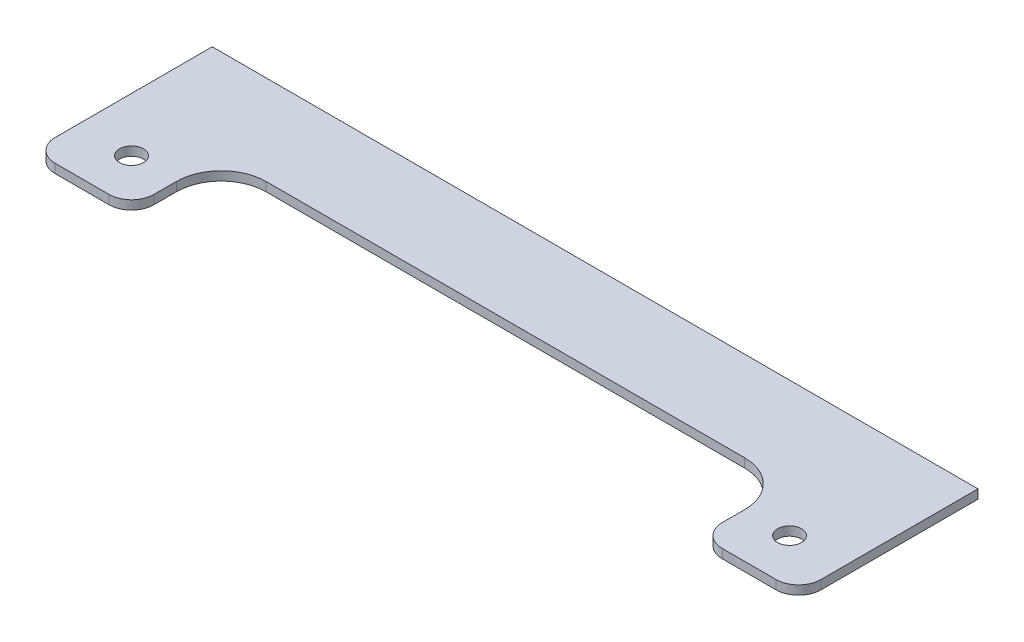
SolidWorks part; units mm, degrees
material "Клен"
ref_plane "Спереди" through (0, 0, 0) normal (0, 0, 1) x (1, 0, 0)
ref_plane "Сверху" through (0, 0, 0) normal (0, 1, 0) x (1, 0, 0)
ref_plane "Справа" through (0, 0, 0) normal (1, 0, 0) x (0, 0, -1)
sketch "Эскиз1" plane through (0, 0, 0) normal (0, 1, 0) x (1, 0, 0)
  line L0 (-330.2029, 15) -> (-330.2029, 120)
  line L5 (-330.2029, 120) -> (181.7971, 120)
  line L6 (181.7971, 120) -> (181.7971, 15)
  line L7 (166.7971, 0) -> (130.7971, 0)
  line L8 (115.7971, 15) -> (115.7971, 30)
  line L9 (85.7971, 60) -> (-234.2029, 60)
  line L10 (-264.2029, 30) -> (-264.2029, 15)
  line L11 (-279.2029, 0) -> (-315.2029, 0)
  arc A0 (-234.2029, 60) -> (-264.2029, 30) centre (-234.2029, 30) ccw
  arc A1 (115.7971, 30) -> (85.7971, 60) centre (85.7971, 30) ccw
  arc A2 (-264.2029, 15) -> (-279.2029, 0) centre (-279.2029, 15) cw
  arc A3 (130.7971, 0) -> (115.7971, 15) centre (130.7971, 15) cw
  arc A4 (-330.2029, 15) -> (-315.2029, 0) centre (-315.2029, 15) ccw
  arc A5 (181.7971, 15) -> (166.7971, 0) centre (166.7971, 15) cw
  dimension "D4" = 30
  dimension "D5" = 30
  dimension "D6" = 15
  dimension "D7" = 15
  dimension "D8" = 15
  dimension "D9" = 15
  dimension "D1" = 512
  dimension "D2" = 120
  dimension "D3" = 66
  dimension "D10" = 60
extrude "Бобышка-Вытянуть1" add sketch "Эскиз1" along normal blind 6
sketch "Эскиз7" plane through (0, 0, 0) normal (0, 1, 0) x (1, 0, 0)
  circle A0 centre (-294.1328, 29.9296) radius 8
  point P0 (-285.474, 27.9199)
extrude "Вырез-Вытянуть1" cut sketch "Эскиз7" against normal blind 5 and the other way blind 14
sketch "Эскиз8" plane through (0, 0, 0) normal (0, 1, 0) x (1, 0, 0)
  circle A0 centre (145.8675, 29.9296) radius 8
extrude "Вырез-Вытянуть2" cut sketch "Эскиз8" against normal blind 5 and the other way blind 11
